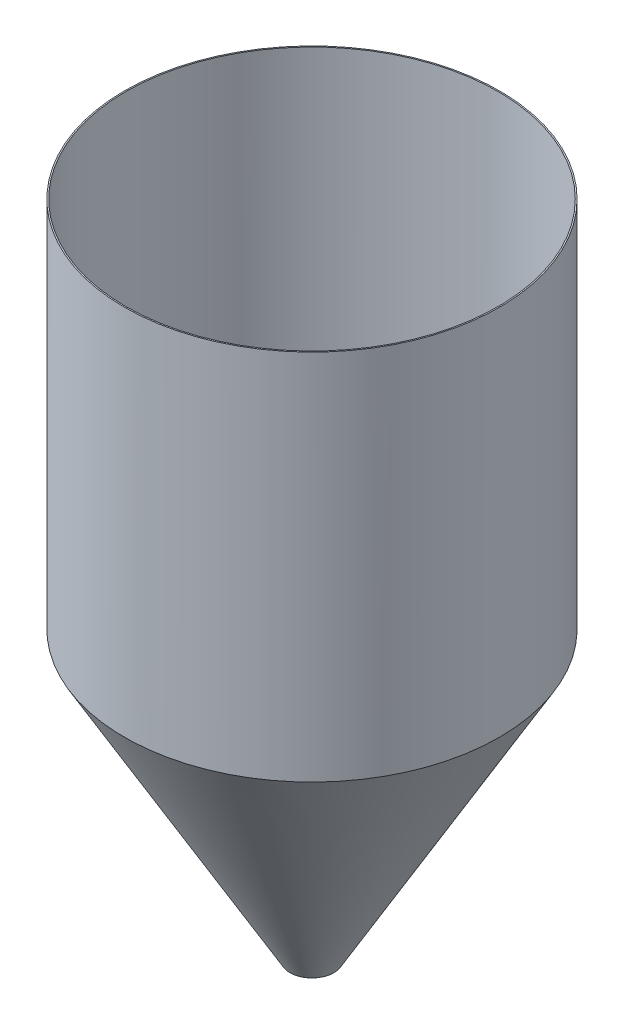
SolidWorks part; units mm, degrees
material "AISI 304"
ref_plane "Front Plane" through (0, 0, 0) normal (0, 0, 1) x (1, 0, 0)
ref_plane "Top Plane" through (0, 0, 0) normal (0, 1, 0) x (1, 0, 0)
ref_plane "Right Plane" through (0, 0, 0) normal (1, 0, 0) x (0, 0, -1)
sketch "Sketch7" plane through (0, 0, 0) normal (0, 1, 0) x (1, 0, 0)
  circle A0 centre (0, 0) radius 228.6
  circle A1 centre (0, 0) radius 230.1875
  dimension "D1" = 457.2
  dimension "D2" = 1.5875
extrude "Boss-Extrude1" add sketch "Sketch7" along normal blind 457.2
sketch "Sketch8" plane through (0, 0, 0) normal (0, 0, 1) x (1, 0, 0)
  line L0 (0, 0) -> (0, -395.9468) construction
  line L1 (0, -395.9468) -> (228.6, 0) construction
  line L2 (-228.6, 0) -> (228.6, 0) construction
  line L3 (-230.1875, 0) -> (230.1875, 0) construction
  line L4 (228.6, 0) -> (230.1875, 0)
  line L5 (228.6, 0) -> (25.4, -351.9527)
  line L6 (25.4, -351.9527) -> (26.9875, -351.9527)
  line L7 (26.9875, -351.9527) -> (230.1875, 0)
  dimension "D1" = 457.2
  dimension "D2" = 457.2
  dimension "D3" = 406.4
revolve "Revolve1" add sketch "Sketch8" angle 360 about L0
